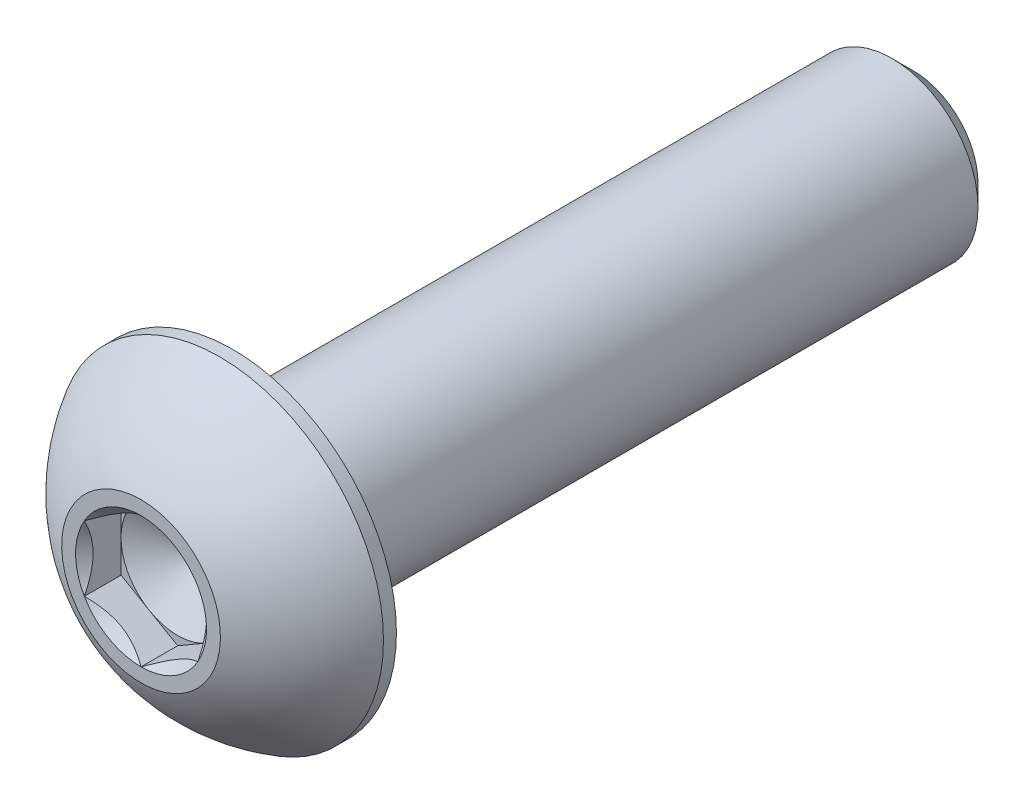
SolidWorks part; units mm, degrees
ref_plane "Front Plane" through (0, 0, 0) normal (0, 0, 1) x (1, 0, 0)
ref_plane "Top Plane" through (0, 0, 0) normal (0, 1, 0) x (1, 0, 0)
ref_plane "Right Plane" through (0, 0, 0) normal (1, 0, 0) x (0, 0, -1)
sketch "Sketch1" plane through (0, 0, 0) normal (1, 0, 0) x (0, 0, -1)
  line L0 (-10.8077, 0) -> (10.8077, 0) construction
  line L1 (-8.2423, 4.5847) -> (-8.2423, -4.5847) construction
  line L2 (-10.8077, 1.5875) -> (-10.8077, -1.5875) construction
  line L3 (10.8077, 2.413) -> (10.8077, -2.413) construction
  line L4 (10.7581, 2.4989) -> (11.155, 1.8115) construction
  line L5 (11.155, 1.8115) -> (11.5518, 2.4989) construction
  line L6 (11.5518, 2.4989) -> (10.7581, 2.4989) construction
  line L7 (11.155, 2.4989) -> (11.155, 2.413) construction
  line L8 (11.155, 1.8115) -> (11.155, 1.8974) construction
  line L9 (11.1054, 1.8974) -> (11.2046, 1.8974)
  line L10 (-10.8077, 2.2225) -> (-10.8077, -2.2225) construction
  line L11 (-8.2423, 4.5847) -> (-8.6052, 4.5847) construction
  line L12 (-10.8077, 1.5875) -> (-9.7815, 1.5875) construction
  line L13 (-9.7815, 1.5875) -> (-8.865, 0) construction
  point P5 (-8.2423, 0)
  point P10 (8.0296, -2.413)
  dimension "Drive Size" = 3.175
  dimension "Head Diameter" = 9.1694
  dimension "Head Height" = 2.5654
  dimension "Screw Size Decimal Equivalent" = 4.826
  dimension "Length" = 19.05
  dimension "D1" = 2.7781
  dimension "Pitch" = 0.7937
  dimension "D2" = 0.0992
  dimension "D3" = 4.445
  dimension "D4" = 0.3629
  dimension "D5" = 60
  dimension "D6" = 1.0262
sketch "Sketch2" plane through (0, 0, 0) normal (1, 0, 0) x (0, 0, -1)
  line L0 (-10.8077, 1.5875) -> (-10.8077, 2.2225)
  line L1 (-8.6052, 4.5847) -> (-8.2423, 4.5847)
  line L2 (-8.2423, 4.5847) -> (-8.2423, 2.413)
  line L3 (-8.2423, 4.5847) -> (-8.2423, -4.5847) construction
  line L4 (-8.2423, 2.413) -> (10.2124, 2.413)
  line L5 (10.8077, 1.8177) -> (10.8077, 0)
  line L6 (-10.8077, 1.5875) -> (-9.7815, 1.5875)
  line L7 (-9.7815, 1.5875) -> (-8.865, 0)
  line L8 (10.8077, 0) -> (-8.865, 0)
  line L9 (10.2124, 2.413) -> (10.8077, 1.8177)
  line L10 (10.2124, -2.413) -> (10.2124, 2.413) construction
  arc A0 (-8.6052, 4.5847) -> (-10.8077, 2.2225) centre (-6.0561, 0) ccw
  point P13 (10.8077, 2.413)
  point P25 (10.2124, 0)
  dimension "D1" = 0.5953
  dimension "D2" = 45
revolve "Revolve1" add sketch "Sketch2" angle 360 about L0
sketch "Sketch3" plane through (0, 0, 0) normal (0, 0, 1) x (1, 0, 0)
  line L1 (0, 1.8331) -> (-1.5875, 0.9165)
  line L2 (-1.5875, 0.9165) -> (-1.5875, -0.9165)
  line L3 (-1.5875, -0.9165) -> (0, -1.8331)
  line L4 (0, -1.8331) -> (1.5875, -0.9165)
  line L5 (1.5875, -0.9165) -> (1.5875, 0.9165)
  line L6 (1.5875, 0.9165) -> (0, 1.8331)
  circle A0 centre (0, 0) radius 1.5875 construction
extrude "Cut-Extrude1" cut sketch "Sketch3" along normal through all from vertex starting at point (0, 1.5875, 9.7815)
sketch "Sketch4" plane through (0, 0, 10.8077) normal (0, 0, 1) x (1, 0, 0)
  circle A0 centre (0, 0) radius 1.8331
extrude "Cut-Extrude2" cut sketch "Sketch4" against normal up to next (21.6154 mm away) draft 45
sketch "Sketch9" plane through (0, 0, 0) normal (1, 0, 0) x (0, 0, -1)
  line L0 (10.8077, -2.413) -> (-8.2423, -2.413) construction
  line L1 (-8.2423, -2.413) -> (10.2124, -2.413) construction
  line L2 (10.8077, -1.8177) -> (10.8077, 1.8177) construction
  line L3 (-8.2423, -2.413) -> (-8.2423, 2.413) construction
  point P9 (9.6171, -2.413)
  dimension "D1" = 1.1906
sketch "Sketch5" [suppressed] plane through (0, 0, -10.8077) normal (0, 0, -1) x (-1, 0, 0)
  circle A0 centre (0, 0) radius 2.413
ref_axis "Center Axis1" through (0, 0, -89.0628) along (0, 0, 1)
ref_plane "Contact Plane1" through (0, 0, -10.8077) normal (0, 0, 1) x (1, 0, 0)
ref_plane "Contact Plane2" through (0, 0, 8.2423) normal (0, 0, 1) x (1, 0, 0)
split "Split1" [suppressed] bodies to split 104
curve "Helix/Spiral1" [suppressed] pitch 0.7937 height 19.8438 turns 25
sketch "Sketch6" [suppressed] plane through (0, 0, 0) normal (1, 0, 0) x (0, 0, -1)
  line L0 (10.8077, 2.413) -> (11.5022, 2.413)
  line L1 (11.5022, 2.413) -> (11.2046, 1.8974)
  line L2 (11.1054, 1.8974) -> (11.2046, 1.8974)
  line L3 (11.1054, 1.8974) -> (10.8077, 2.413)
  line L4 (11.155, 1.8115) -> (11.5518, 2.4989) construction
sweep "Cut-Sweep1" [suppressed] cut profiles "Sketch6" path "Helix/Spiral1"
sketch "Sketch10" [suppressed] plane through (0, 0, 8.2423) normal (0, 0, -1) x (-1, 0, 0)
  circle A0 centre (0, 0) radius 2.4251
  dimension "D1" = 4.8501
extrude "Boss-Extrude1" [suppressed] add sketch "Sketch10" along normal through all draft 30
equation "\"D2@Sketch1\"=\"Pitch@Sketch1\"*.125"
equation "\"D1@Sketch1\"=\"Pitch@Sketch1\"*3.5"
equation "\"D3@Sketch1\"=\"Drive Size@Sketch1\"*1.4"
equation "\"D4@Sketch1\"=(\"D3@Sketch1\"-\"Drive Size@Sketch1\")/3.5"
equation "\"D6@Sketch1\"=\"Head Height@Sketch1\"*.40"
equation "\"D1@Sketch2\"=\"Pitch@Sketch1\"*.750"
equation "\"D4@Helix/Spiral1\"=\"Pitch@Sketch1\""
equation "\"D3@Helix/Spiral1\" = \"D4@Helix/Spiral1\" + \"Length@Sketch1\""
equation "\"D1@Sketch9\"=\"Pitch@Sketch1\"*1.5"
equation "\"D1@Sketch10\"=\"Screw Size Decimal Equivalent@Sketch1\"*1.005"
